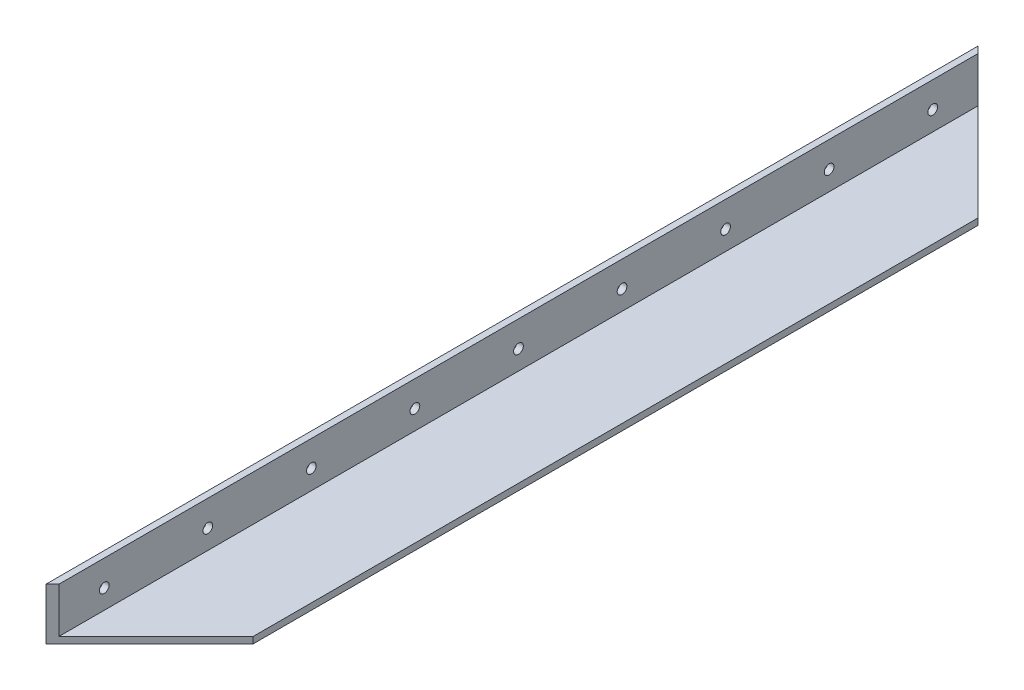
SolidWorks part; units mm, degrees
material "6063-T1"
ref_plane "Front Plane" through (0, 0, 0) normal (0, 0, 1) x (1, 0, 0)
ref_plane "Top Plane" through (0, 0, 0) normal (0, 1, 0) x (1, 0, 0)
ref_plane "Right Plane" through (0, 0, 0) normal (1, 0, 0) x (0, 0, -1)
sketch "Sketch1" plane through (0, 0, 0) normal (0, 0, 1) x (1, 0, 0)
  line L1 (0, 0) -> (50.8, 0)
  line L2 (0, 0) -> (0, 25.4)
  line L3 (0, 25.4) -> (50.8, 25.4)
  line L4 (50.8, 0) -> (50.8, 25.4)
  line L5 (50.8, 25.4) -> (3.175, 25.4)
  line L6 (50.8, 25.4) -> (50.8, 3.175)
  line L7 (50.8, 3.175) -> (3.175, 3.175)
  line L8 (3.175, 25.4) -> (3.175, 3.175)
  dimension "D1" = 3.175
  dimension "D2" = 3.175
  dimension "D3" = 25.4
  dimension "D4" = 50.8
extrude "Boss-Extrude1" add sketch "Sketch1" along normal blind 457.2 contours L8 L3 L2 L1 L4 L7 region at (0.568, 12.7, 0)
sketch "Sketch2" plane through (0, 0, 0) normal (-1, 0, 0) x (0, 0, 1)
  line L0 (457.2, 0) -> (0, 0) construction
  line L1 (457.2, 0) -> (457.2, 25.4) construction
  circle A0 centre (431.8, 12.7) radius 2.3813
  circle A1 centre (381, 12.7) radius 2.3813
  circle A2 centre (330.2, 12.7) radius 2.3813
  circle A3 centre (279.4, 12.7) radius 2.3813
  circle A4 centre (228.6, 12.7) radius 2.3813
  circle A5 centre (177.8, 12.7) radius 2.3813
  circle A6 centre (127, 12.7) radius 2.3813
  circle A7 centre (76.2, 12.7) radius 2.3813
  circle A8 centre (25.4, 12.7) radius 2.3813
  circle A9 centre (-25.4, 12.7) radius 2.3813
  dimension "D3" = 4.7625
  dimension "D1" = 12.7
  dimension "D2" = 25.4
  dimension "D4" = 10
extrude "Cut-Extrude1" cut sketch "Sketch2" against normal through all
chamfer "Chamfer1" distance 50.8 angle 45 1 edges at (50.8, 1.5875, 457.2)
chamfer "Chamfer2" distance 50.8 angle 45 1 edges at (50.8, 1.5875, 0)
